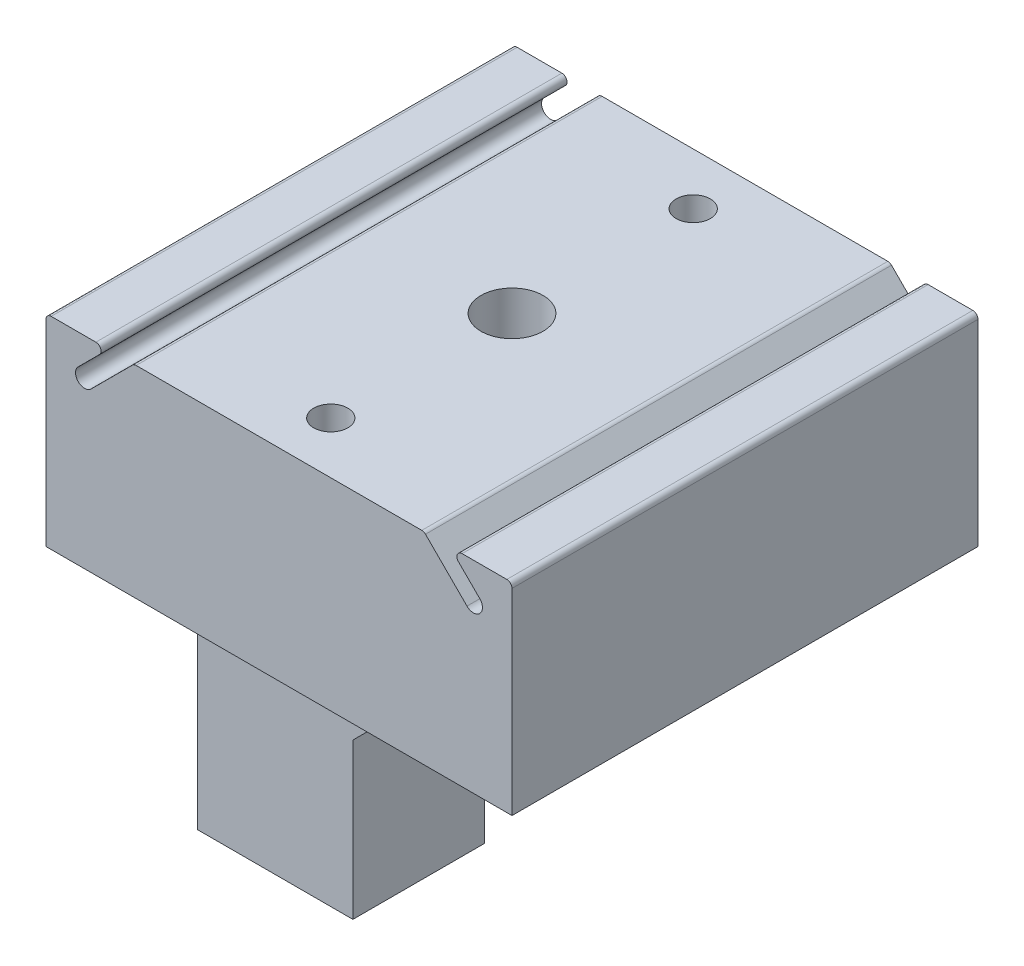
SolidWorks part; units mm, degrees
material "ABS"
ref_plane "Front Plane" through (0, 0, 0) normal (0, 0, 1) x (1, 0, 0)
ref_plane "Top Plane" through (0, 0, 0) normal (0, 1, 0) x (1, 0, 0)
ref_plane "Right Plane" through (0, 0, 0) normal (1, 0, 0) x (0, 0, -1)
sketch "Sketch1" plane through (0, 0, 0) normal (0, 0, 1) x (1, 0, 0)
  line L0 (22.5, 0) -> (-22.5, 0) construction
  line L6 (-22.5, 9.5) -> (22.5, 9.5)
  line L9 (-22.5, 9.5) -> (-22.5, -10)
  line L10 (-22.5, -10) -> (22.5, -10)
  line L11 (22.5, 9.5) -> (22.5, -10)
  point P8 (0, 0)
  dimension "D2" = 9.5
  dimension "D1" = 45
  dimension "D3" = 10
extrude "Boss-Extrude1" add sketch "Sketch1" along normal mid plane 45
sketch "Sketch3" plane through (0, 0, 0) normal (0, 0, 1) x (1, 0, 0)
  line L0 (0, 9.5) -> (0, -10)
  line L1 (0, -10) -> (8, -10)
  line L2 (8, -10) -> (8, -3.25)
  line L3 (8, -3.25) -> (6, -3.25)
  line L4 (6, -3.25) -> (6, 2.75)
  line L5 (6, 2.75) -> (8, 2.75)
  line L6 (8, 2.75) -> (8, 9.5)
  line L7 (8, 9.5) -> (0, 9.5)
  line L8 (22.5, 9.5) -> (-22.5, 9.5) construction
  line L9 (-22.5, -10) -> (22.5, -10) construction
  dimension "D1" = 6
  dimension "D2" = 8
  dimension "D3" = 6
revolve "Cut-Revolve1" [suppressed] cut sketch "Sketch3" angle 360 about L0
hole_wizard "M4x0.7 Tapped Hole2" positions "Sketch5" profile "Sketch4" tap size "M4x0.7" standard "ANSI Metric" end condition through all
sketch "Sketch5" plane through (0, -10, 0) normal (0, -1, 0) x (-1, 0, 0)
  line L0 (0, 17.5) -> (0, -17.5) construction
  line L2 (22.5, -22.5) -> (-22.5, -22.5) construction
  point P0 (0, -17.5)
  point P2 (0, 17.5)
  dimension "D1" = 5
sketch "Sketch4" plane through (0, -10, 17.5) normal (1, 0, 0) x (0, 0, -1)
  line L0 (0, 0) -> (0, 19.5)
  line L1 (0, 19.5) -> (1.65, 19.5)
  line L2 (1.65, 19.5) -> (1.65, 0)
  line L5 (1.65, 0) -> (0, 0)
  line L11 (0, -6.35) -> (0, 107.95) construction
  dimension "Thru Tap Drill Dia." = 3.3
  dimension "Thru Tap Drill Depth" = 19.5
cosmetic thread "Hole Thread1" parameters "D2"=4
cosmetic thread "Hole Thread2" parameters "D2"=4
sketch "Sketch7" plane through (0, 0, 0) normal (0, 0, 1) x (1, 0, 0)
  line L0 (-22.5, -7.5) -> (-24, -7.5)
  line L1 (-24, -7.5) -> (-24, -42.5)
  line L2 (-22.5, -10) -> (-22.5, -7.5)
  line L3 (-22.5, 9.5) -> (-22.5, -10) construction
  line L5 (8.5, -10) -> (-22.5, -10)
  line L7 (-24, -42.5) -> (-9, -42.5)
  line L8 (-9, -42.5) -> (-9, -27.5)
  line L9 (-9, -27.5) -> (8.5, -10)
  dimension "D1" = 24
  dimension "D2" = 35
  dimension "D3" = 15
  dimension "D4" = 45
  dimension "D5" = 2.5
  dimension "D6" = 15
extrude "Boss-Extrude3" add sketch "Sketch7" against normal mid plane 12.725
hole_wizard "M4x0.7 Tapped Hole1" positions "Sketch9" profile "Sketch8" tap size "M4x0.7" standard "ANSI Metric"
sketch "Sketch9" plane through (-24, 0, 0) normal (1, 0, 0) x (0, 0, -1)
  line L0 (6.3625, -42.5) -> (-6.3625, -42.5) construction
  point P0 (0, -37.5)
  point P2 (0, -22.5)
  dimension "D1" = 15
  dimension "D2" = 5
sketch "Sketch8" plane through (-24, -37.5, 0) normal (0, 1, 0) x (0, 0, 1)
  line L0 (0, 0) -> (0, 10.9914)
  line L1 (0, 10.9914) -> (1.65, 10)
  line L2 (1.65, 10) -> (1.65, 0)
  line L5 (1.65, 0) -> (0, 0)
  line L10 (0, 10.9914) -> (-1.65, 10) construction
  line L11 (0, -6.35) -> (0, 107.95) construction
  dimension "Tap Drill Dia." = 3.3
  dimension "Tap Drill Depth" = 10
  dimension "Drill Angle" = 118
cosmetic thread "Hole Thread5" parameters "D1"=8, "D2"=4
cosmetic thread "Hole Thread6" parameters "D1"=8, "D2"=4
sketch "Sketch10" plane through (0, 0, -6.3625) normal (0, 0, -1) x (-1, 0, 0)
  line L0 (22.5, -10) -> (24, -11.5)
  line L1 (24, -7.5) -> (24, -42.5) construction
  line L2 (24, -11.5) -> (24, -7.5)
  line L3 (24, -7.5) -> (22.5, -7.5)
  line L4 (22.5, -7.5) -> (22.5, -10)
  dimension "D1" = 45
extrude "Cut-Extrude2" cut sketch "Sketch10" against normal blind 85
sketch "Sketch2" plane through (0, 9.5, 0) normal (0, 1, 0) x (1, 0, 0)
  circle A0 centre (0, 0) radius 3
  dimension "D1" = 6
extrude "Cut-Extrude1" cut sketch "Sketch2" against normal blind 50
sketch "Sketch11" plane through (0, 0, 0) normal (0, 0, 1) x (1, 0, 0)
  line L0 (-16.4749, 9.5) -> (-20.0104, 5.9645)
  line L1 (22.5, 9.5) -> (-22.5, 9.5) construction
  line L2 (-20.0104, 5.9645) -> (-18.773, 4.727)
  line L3 (-18.773, 4.727) -> (-14, 9.5)
  line L4 (-14, 9.5) -> (-16.4749, 9.5)
  line L5 (0, 0) -> (0, 9.5) construction
  line L6 (14, 9.5) -> (16.4749, 9.5)
  line L7 (18.773, 4.727) -> (14, 9.5)
  line L8 (20.0104, 5.9645) -> (18.773, 4.727)
  line L9 (16.4749, 9.5) -> (20.0104, 5.9645)
  dimension "D1" = 45
  dimension "D2" = 1.75
  dimension "D3" = 6.75
  dimension "D4" = 14
extrude "Cut-Extrude3" cut sketch "Sketch11" against normal mid plane 50
fillet "Fillet1" 2 edges at (-20.0104, 5.9645, 0) (-18.773, 4.727, 0) type full round first side face at (-18.2426, 7.7322, 0) second side face at (-16.3865, 7.1135, 0) middle face at (-19.3917, 5.3457, 0)
fillet "Fillet2" 2 edges at (18.773, 4.727, 0) (20.0104, 5.9645, 0) type full round first side face at (16.3865, 7.1135, 0) second side face at (18.2426, 7.7322, 0) middle face at (19.3917, 5.3457, 0)
fillet "Fillet3" radius 0.5 6 edges at (-22.5, 9.5, 0) (-16.4749, 9.5, 0) (22.5, 9.5, 0) (16.4749, 9.5, 0) (-14, 9.5, 0) (14, 9.5, 0)
